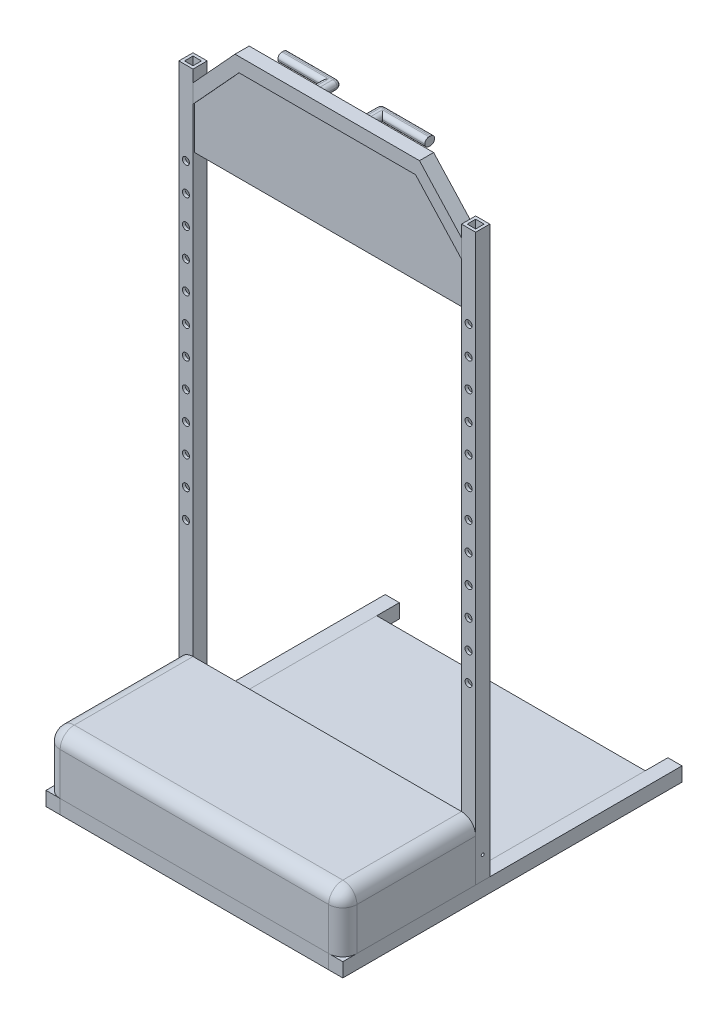
SolidWorks part; units mm, degrees
ref_plane "Front Plane" through (0, 0, 0) normal (0, 0, 1) x (1, 0, 0)
ref_plane "Top Plane" through (0, 0, 0) normal (0, 1, 0) x (1, 0, 0)
ref_plane "Right Plane" through (0, 0, 0) normal (1, 0, 0) x (0, 0, -1)
sketch "Sketch1" plane through (0, 0, 0) normal (0, 1, 0) x (1, 0, 0)
  line L0 (-525, -1151.5385) -> (-525, 48.4615)
  line L1 (-525, 48.4615) -> (-475, 48.4615)
  line L2 (-475, 48.4615) -> (-475, -1151.5385)
  line L3 (-475, -1151.5385) -> (-525, -1151.5385)
  line L4 (475, 48.4615) -> (475, -1151.5385)
  line L5 (475, -1151.5385) -> (525, -1151.5385)
  line L6 (525, -1151.5385) -> (525, 48.4615)
  line L7 (525, 48.4615) -> (475, 48.4615)
  line L8 (0, 0) -> (-475, 0)
  line L9 (0, 0) -> (475, 0)
  dimension "D1" = 50
  dimension "D2" = 50
  dimension "D3" = 475
  dimension "D4" = 475
  dimension "D5" = 1200
  dimension "D6" = 1200
extrude "Boss-Extrude1" add sketch "Sketch1" along normal blind 50 contours L3 L2 L1 L0 | L6 L7 L4 L5 region at (500, 0, 551.5385) region at (-500, 0, 551.5385)
sketch "Sketch2" plane through (0, 0, 0) normal (0, -1, 0) x (1, 0, 0)
  line L0 (-475, 1001.5385) -> (475, 1001.5385)
  line L1 (-475, -48.4615) -> (-475, 1151.5385) construction
  line L2 (475, -48.4615) -> (475, 1151.5385) construction
  line L3 (-475, 1001.5385) -> (-475, 1051.5385)
  line L4 (-475, 1051.5385) -> (475, 1051.5385)
  line L5 (475, 1051.5385) -> (475, 1001.5385)
  line L6 (-475, 1151.5385) -> (-475, 1001.5385)
  line M8 (475, 1151.5385) -> (475, -48.4615)
  dimension "D1" = 150
  dimension "D2" = 50
extrude "Boss-Extrude2" add sketch "Sketch2" against normal blind 50 separate body contours L4 L3 L0 M8 region at (0, 0, 1026.5385)
sketch "Sketch3" plane through (0, 50, 0) normal (0, 1, 0) x (1, 0, 0)
  line L11 (-525, -1151.5385) -> (-525, 48.4615) construction
  line L12 (-525, -681.5385) -> (-525, -631.5385)
  line L13 (-525, -631.5385) -> (-475, -631.5385)
  line L14 (-475, 48.4615) -> (-475, -1151.5385) construction
  line L15 (-475, -631.5385) -> (-475, -681.5385)
  line L16 (-475, -681.5385) -> (-525, -681.5385)
  line L17 (475, -681.5385) -> (475, -631.5385)
  line L19 (475, -631.5385) -> (525, -631.5385)
  line L21 (525, -631.5385) -> (525, -681.5385)
  line L22 (525, -681.5385) -> (475, -681.5385)
  point P0 (0, 0)
  dimension "D2" = 50
extrude "Boss-Extrude3" add sketch "Sketch3" along normal blind 2000 separate body
sketch "Sketch6" plane through (0, 0, 631.5385) normal (0, 0, -1) x (-1, 0, 0)
  line L1 (-475, 2050) -> (-475, 50) construction
  line L4 (475, 1942.6335) -> (430.5496, 1991.1256)
  line L7 (430.5496, 1991.1256) -> (312.4166, 2120)
  line L9 (-442.5309, 1978.0581) -> (-312.4312, 2120)
  line L10 (-326.3491, 2170) -> (326.3491, 2170)
  line L11 (-326.3491, 2170) -> (-475, 2007.8183)
  line L12 (326.3491, 2170) -> (475, 2007.8183)
  line L13 (475, 2050) -> (475, 50) construction
  line L15 (-475, 2007.8183) -> (-475, 1942.6335)
  line L16 (-312.4312, 2120) -> (312.4166, 2120)
  line L17 (475, 2007.8183) -> (475, 1942.6335)
  line L18 (-442.5309, 1978.0581) -> (-475, 1942.6335)
  dimension "D1" = 220
  dimension "D2" = 220
  dimension "D3" = 137.493
  dimension "D4" = 137.49
extrude "Boss-Extrude4" add sketch "Sketch6" against normal blind 50 separate body
sketch "Sketch8" plane through (0, 2050, 0) normal (0, 1, 0) x (1, 0, 0)
  line L0 (-515, -641.5385) -> (-515, -671.5385)
  line L1 (-515, -671.5385) -> (-485, -671.5385)
  line L2 (-485, -671.5385) -> (-485, -641.5385)
  line L3 (-485, -641.5385) -> (-515, -641.5385)
  line L4 (-525, -657.9132) -> (-515, -657.9132)
  line L5 (-525, -631.5385) -> (-525, -681.5385) construction
  line L6 (-491.9197, -671.5385) -> (-491.9197, -681.5385)
  line L8 (-500, -641.5385) -> (-500, -631.5385)
  line L9 (-475, -631.5385) -> (-525, -631.5385) construction
  line L10 (-485, -648.1401) -> (-475, -648.1401)
  line L11 (-475, -681.5385) -> (-475, -631.5385) construction
  line L12 (485, -671.5385) -> (485, -641.5385)
  line L13 (485, -641.5385) -> (515, -641.5385)
  line L14 (515, -641.5385) -> (515, -671.5385)
  line L15 (515, -671.5385) -> (485, -671.5385)
  line L16 (500, -671.5385) -> (500, -681.5385)
  line L17 (475, -681.5385) -> (525, -681.5385) construction
  line L18 (515, -657.9132) -> (525, -657.9132)
  line L19 (525, -681.5385) -> (525, -631.5385) construction
  line L20 (500, -641.5385) -> (500, -631.5385)
  line L22 (485, -657.9132) -> (475, -657.9132)
  line L23 (475, -631.5385) -> (475, -681.5385) construction
  point P10 (0, 0)
  point P40 (0, 0)
  dimension "D1" = 10
  dimension "D2" = 10
  dimension "D3" = 10
  dimension "D4" = 10
  dimension "D5" = 10
  dimension "D6" = 10
  dimension "D7" = 10
  dimension "D8" = 10
extrude "Cut-Extrude1" cut sketch "Sketch8" against normal blind 1980 contours L15 L14 L13 L12 | L2 L3 L0 L1 region at (-500, 2050, 656.5385) region at (500, 2050, 656.5385)
sketch "Sketch9" plane through (0, 50, 0) normal (0, 1, 0) x (1, 0, 0)
  line L0 (-525, -681.5385) -> (-525, -1151.5385)
  line L1 (-475, -1151.5385) -> (-525, -1151.5385) construction
  line L2 (-525, -1151.5385) -> (-525, 48.4615) construction
  line L3 (-525, -1151.5385) -> (525, -1151.5385)
  line L4 (525, -1151.5385) -> (525, -681.5385)
  line L5 (525, -681.5385) -> (-525, -681.5385)
  point P7 (0, 0)
  point P12 (0, 0)
  point P13 (0, 0)
  point P14 (0, 0)
extrude "Boss-Extrude5" add sketch "Sketch9" along normal blind 200 separate body
sketch "Sketch10" plane through (0, 0, 1001.5385) normal (0, 0, -1) x (-1, 0, 0)
  line L4 (-475, 50) -> (-475, 0)
  line L5 (-475, 0) -> (475, 0)
  line L7 (475, 0) -> (-475, 0) construction
  line L8 (475, 0) -> (475, 50)
  line L9 (475, 50) -> (-475, 50)
  point P2 (0, 0)
  point P3 (0, 0)
  point P4 (0, 0)
  point P6 (0, 0)
extrude "Boss-Extrude7" add sketch "Sketch10" along normal blind 320 separate body
sketch "Sketch11" plane through (0, 0, 1051.5385) normal (0, 0, 1) x (1, 0, 0)
  line L0 (-475, 50) -> (-475, 0)
  line L1 (-475, 0) -> (475, 0)
  line L2 (-475, 0) -> (475, 0) construction
  line L3 (475, 0) -> (475, 50)
  line L4 (475, 50) -> (-475, 50)
extrude "Boss-Extrude8" add sketch "Sketch11" along normal blind 100 separate body
fillet "Fillet1" radius 50 1 edges at (0, 250, 1151.5385)
fillet "Fillet2" radius 50 3 edges at (525, 125, 1151.5385) (525, 235.3553, 1136.8938) (525, 250, 891.5385)
fillet "Fillet3" radius 50 3 edges at (-525, 125, 1151.5385) (-525, 235.3553, 1136.8938) (-525, 250, 891.5385)
sketch "Sketch15" plane through (0, 0, 631.5385) normal (0, 0, -1) x (-1, 0, 0)
  line L0 (-525, 2050) -> (-525, 50) construction
  line L1 (-525, 1756.2545) -> (-475, 1756.2545)
  line L2 (-475, 2050) -> (-475, 50) construction
  line L3 (475, 1756.2545) -> (525, 1756.2545)
  line L4 (475, 2050) -> (475, 50) construction
  line L5 (525, 2050) -> (525, 50) construction
  circle A0 centre (-500, 1756.2545) radius 12.5
  circle A1 centre (500, 1756.2545) radius 12.5
  circle A2 centre (-500, 1656.2545) radius 12.5
  circle A3 centre (500, 1656.2545) radius 12.5
  circle A4 centre (-500, 1556.2545) radius 12.5
  circle A5 centre (500, 1556.2545) radius 12.5
  circle A6 centre (-500, 1456.2545) radius 12.5
  circle A7 centre (500, 1456.2545) radius 12.5
  circle A8 centre (-500, 1356.2545) radius 12.5
  circle A9 centre (500, 1356.2545) radius 12.5
  circle A10 centre (-500, 1256.2545) radius 12.5
  circle A11 centre (500, 1256.2545) radius 12.5
  circle A12 centre (-500, 1156.2545) radius 12.5
  circle A13 centre (500, 1156.2545) radius 12.5
  circle A14 centre (-500, 1056.2545) radius 12.5
  circle A15 centre (500, 1056.2545) radius 12.5
  circle A16 centre (-500, 956.2545) radius 12.5
  circle A17 centre (500, 956.2545) radius 12.5
  circle A18 centre (-500, 856.2545) radius 12.5
  circle A19 centre (500, 856.2545) radius 12.5
  circle A20 centre (-500, 756.2545) radius 12.5
  circle A21 centre (500, 756.2545) radius 12.5
  circle A22 centre (-500, 656.2545) radius 12.5
  circle A23 centre (500, 656.2545) radius 12.5
  dimension "D1" = 25
  dimension "D2" = 25
  dimension "D3" = 12
extrude "Cut-Extrude4" cut sketch "Sketch15" against normal blind 50 contours L1 A0 | L1 A0 | A2 | A4 | A6 | A8 | A10 | A12 | A14 | L3 A1 | L3 A1 | A3 | A5 | A7 | A9 | A16 | A18 | A20 | A22 | A11 | A13 | A15 | A17 | A19 | A21 | A23 region at (500, 1761.5597, 631.5385) region at (500, 1750.9494, 631.5385) region at (-500, 1761.5597, 631.5385) region at (-500, 1750.9494, 631.5385) region at (500, 1656.2545, 631.5385) region at (-500, 1656.2545, 631.5385) region at (500, 1556.2545, 631.5385) region at (-500, 1556.2545, 631.5385) region at (500, 1456.2545, 631.5385) region at (-500, 1456.2545, 631.5385) region at (500, 1356.2545, 631.5385) region at (-500, 1356.2545, 631.5385) region at (500, 1256.2545, 631.5385) region at (500, 1156.2545, 631.5385) region at (500, 1056.2545, 631.5385)
sketch "Sketch17" plane through (0, 0, 631.5385) normal (0, 0, -1) x (-1, 0, 0)
  line L0 (-475, 1942.6335) -> (-475, 1792.1994)
  line L1 (-475, 2050) -> (-475, 50) construction
  line L2 (-475, 1792.1994) -> (475, 1792.1994)
  line L3 (475, 2050) -> (475, 50) construction
  line L4 (475, 1792.1994) -> (475, 1942.6335)
  line L5 (475, 1942.6335) -> (312.4166, 2120)
  line L6 (312.4166, 2120) -> (475, 1942.6335) construction
  line L7 (312.4166, 2120) -> (-312.4312, 2120)
  line L8 (-312.4312, 2120) -> (-475, 1942.6335)
  dimension "D1" = 150.4341
extrude "Boss-Extrude13" add sketch "Sketch17" against normal blind 45 separate body
sketch "Sketch19" plane through (0, 0, 631.5385) normal (0, 0, -1) x (-1, 0, 0)
  line L0 (-272.3284, 1988.7665) -> (-272.3284, 1912.0744)
  line L1 (-272.3284, 1912.0744) -> (-242.3706, 1912.0744)
  line L2 (-242.3706, 1912.0744) -> (-242.3706, 1960.9057)
  line L3 (-242.3706, 1960.9057) -> (-180.3579, 1960.9057)
  line L4 (-180.3579, 1960.9057) -> (-180.3579, 1988.7665)
  line L5 (-180.3579, 1988.7665) -> (-272.3284, 1988.7665)
  line L6 (-141.1131, 1988.7665) -> (-141.1131, 1912.0744)
  line L7 (-141.1131, 1912.0744) -> (-112.9528, 1912.0744)
  line L8 (-112.9528, 1912.0744) -> (-112.9528, 1988.7665)
  line L9 (-112.9528, 1988.7665) -> (-141.1131, 1988.7665)
  line L10 (-48.2439, 2017.8255) -> (-48.2439, 1912.0744)
  line L11 (-48.2439, 1912.0744) -> (-18.8852, 1912.0744)
  line L12 (-18.8852, 1912.0744) -> (-18.8852, 2017.8255)
  line L13 (-18.8852, 2017.8255) -> (17.0642, 2017.8255)
  line L14 (17.0642, 2017.8255) -> (17.0642, 2045.9859)
  line L15 (17.0642, 2045.9859) -> (-90.784, 2045.9859)
  line L16 (-90.784, 2045.9859) -> (-90.784, 2017.8255)
  line L17 (-90.784, 2017.8255) -> (-48.2439, 2017.8255)
  line L18 (71.8777, 2017.8255) -> (71.8777, 1912.0744)
  line L19 (71.8777, 1912.0744) -> (99.773, 1912.0744)
  line L20 (99.773, 1912.0744) -> (99.773, 2017.8255)
  line L21 (99.773, 2017.8255) -> (142.35, 2017.8255)
  line L22 (142.35, 2017.8255) -> (142.35, 2045.9859)
  line L23 (142.35, 2045.9859) -> (33.4606, 2045.9859)
  line L24 (33.4606, 2045.9859) -> (33.4606, 2017.8255)
  line L25 (33.4606, 2017.8255) -> (71.8777, 2017.8255)
  line L26 (160.7022, 1988.7665) -> (160.7022, 1912.0744)
  line L27 (160.7022, 1912.0744) -> (187.3739, 1912.0744)
  line L28 (187.3739, 1912.0744) -> (187.3739, 1958.7508)
  line L29 (198.1476, 1960.9057) -> (242.0166, 1912.0744)
  line L30 (242.0166, 1912.0744) -> (275.9419, 1912.0744)
  line L31 (275.9419, 1912.0744) -> (232.0729, 1960.9057)
  line L32 (160.7022, 1988.7665) -> (232.0729, 1988.7665)
  line L33 (160.7022, 2045.9859) -> (160.7022, 2017.8255)
  line L34 (160.7022, 2017.8255) -> (232.0729, 2017.8255)
  line L35 (160.7022, 2045.9859) -> (232.0729, 2045.9859)
  line L36 (-272.3284, 2003.4296) -> (-246.6703, 2003.4296)
  line L37 (-226.9126, 2017.8255) -> (-163.753, 2017.8255)
  line L38 (-163.753, 2017.8255) -> (-163.753, 2045.9859)
  line L39 (-163.753, 2045.9859) -> (-226.9126, 2045.9859)
  line L40 (-226.9126, 2045.9859) -> (-238.7348, 2045.9859)
  line L41 (-136.9779, 1873.4631) -> (-136.9779, 1826.4801)
  line L42 (-136.9779, 1826.4801) -> (-109.9029, 1826.4801)
  line L43 (-136.9779, 1873.4631) -> (-109.9029, 1873.4631)
  line L44 (-125.1753, 1862.599) -> (-125.1753, 1856.5312)
  line L45 (-125.1753, 1856.5312) -> (-112.9528, 1856.5312)
  line L46 (-125.1753, 1862.599) -> (-112.9528, 1862.599)
  line L47 (-125.1753, 1845.9513) -> (-125.1753, 1839.5724)
  line L48 (-125.1753, 1839.5724) -> (-112.9528, 1839.5724)
  line L49 (-125.1753, 1845.9513) -> (-112.9528, 1845.9513)
  line L50 (-112.9528, 1845.9513) -> (-109.9029, 1845.9513)
  line L51 (-112.9528, 1839.5724) -> (-109.9029, 1839.5724)
  line L52 (-85.0343, 1873.4631) -> (-66.6752, 1842.7619)
  line L53 (-66.6752, 1842.7619) -> (-66.6752, 1826.4801)
  line L54 (-66.6752, 1826.4801) -> (-57.4956, 1826.4801)
  line L55 (-57.4956, 1826.4801) -> (-57.4956, 1842.7619)
  line L56 (-57.4956, 1842.7619) -> (-41.4704, 1873.4631)
  line L57 (-41.4704, 1873.4631) -> (-50.1843, 1873.4631)
  line L58 (-50.1843, 1873.4631) -> (-62.0854, 1858.1125)
  line L59 (-62.0854, 1858.1125) -> (-75.8547, 1873.4631)
  line L60 (-75.8547, 1873.4631) -> (-85.0343, 1873.4631)
  line L61 (4.7086, 1873.4631) -> (4.7086, 1826.4801)
  line L62 (4.7086, 1826.4801) -> (13.2284, 1826.4801)
  line L63 (13.2284, 1826.4801) -> (13.2284, 1839.5724)
  line L64 (4.7086, 1873.4631) -> (28.4157, 1873.4631)
  line L65 (15.2657, 1862.599) -> (15.2657, 1851.9624)
  line L66 (15.2657, 1851.9624) -> (26.008, 1851.9624)
  line L67 (15.2657, 1862.599) -> (26.008, 1862.599)
  line L68 (22.0959, 1839.5724) -> (33.4606, 1826.4801)
  line L69 (33.4606, 1826.4801) -> (45.4406, 1826.4801)
  line L70 (45.4406, 1826.4801) -> (32.4677, 1841.4251)
  line L71 (62.3238, 1873.4631) -> (62.3238, 1826.4801)
  line L72 (62.3238, 1826.4801) -> (71.8777, 1826.4801)
  line L73 (71.8777, 1826.4801) -> (71.8777, 1873.4631)
  line L74 (71.8777, 1873.4631) -> (62.3238, 1873.4631)
  circle A0 centre (-127.033, 2031.1227) radius 13.873
  circle A1 centre (-199.4893, 1851.9624) radius 11.2617
  circle A2 centre (198.1476, 1851.9624) radius 12.096
  arc A3 (232.0729, 2017.8255) -> (232.0729, 1988.7665) centre (228.8278, 2003.296) cw
  arc A4 (232.0729, 2045.9859) -> (232.0729, 1960.9057) centre (230.1472, 2003.4458) cw
  arc A5 (-272.3284, 2003.4296) -> (-238.7348, 2045.9859) centre (-233.4063, 2007.2423) cw
  arc A6 (-246.6703, 2003.4296) -> (-226.9126, 2017.8255) centre (-227.5737, 1997.9766) cw
  arc A7 (-109.9029, 1873.4631) -> (-102.1486, 1851.9624) centre (-113.2015, 1860.1248) cw
  arc A8 (-109.9029, 1826.4801) -> (-102.1486, 1851.9624) centre (-113.2682, 1841.4251) ccw
  arc A9 (-112.9528, 1862.599) -> (-112.9528, 1856.5312) centre (-112.8849, 1859.5651) cw
  arc A10 (-109.9029, 1845.9513) -> (-109.9029, 1839.5724) centre (-111.2845, 1842.7619) cw
  arc A11 (26.008, 1862.599) -> (26.008, 1851.9624) centre (26.0805, 1857.2807) cw
  arc A12 (28.4157, 1873.4631) -> (32.4677, 1841.4251) centre (26.7494, 1856.9771) cw
  arc A13 (13.2284, 1839.5724) -> (22.0959, 1839.5724) centre (17.6621, 1834.6146) cw
  circle A14 centre (115.4352, 1851.9624) radius 12.8515
  circle A15 centre (115.4352, 1851.9624) radius 25.4976
  arc A16 (187.3739, 1958.7508) -> (198.1476, 1960.9057) centre (193.2488, 1957.3882) cw
extrude "Boss-Extrude14" add sketch "Sketch19" along normal blind 10 separate body
sketch "Sketch21" plane through (0, 0, 631.5385) normal (0, 0, -1) x (-1, 0, 0)
  line L0 (-270, 1792.1994) -> (0, 1792.1994)
  line L1 (-475, 1792.1994) -> (475, 1792.1994) construction
  line L2 (0, 1792.1994) -> (270, 1792.1994)
  line L3 (270, 1792.1994) -> (145.7896, 1644.1712)
  line L4 (145.7896, 1644.1712) -> (-145.7896, 1644.1712)
  line L5 (-145.7896, 1644.1712) -> (-270, 1792.1994)
  line L6 (-132.9099, 1690.9003) -> (132.3288, 1690.9003)
  line L9 (-217.9099, 1792.1994) -> (-132.9099, 1690.9003)
  line L10 (217.3288, 1792.1994) -> (132.3288, 1690.9003)
  line M9 (-475, 1792.1994) -> (475, 1792.1994)
  dimension "D1" = 130
  dimension "D2" = 130
  dimension "D3" = 270
  dimension "D4" = 270
  dimension "D5" = 130
  dimension "D6" = 130
  dimension "D7" = 85
  dimension "D8" = 85
extrude "Boss-Extrude16" [suppressed] add sketch "Sketch21" against normal blind 40 separate body contours L2 L10 L6 L9 L5 L4 L3 M9
sketch "Sketch25" plane through (0, 0, 631.5385) normal (0, 0, -1) x (-1, 0, 0)
  line L0 (-326.3491, 2170) -> (326.3491, 2170)
  line L1 (0, 2170) -> (-0.0073, 2120)
  line L2 (-312.4312, 2120) -> (312.4166, 2120) construction
  line L3 (-0.0037, 2145) -> (-90.0037, 2145)
  line L4 (-0.0037, 2145) -> (89.9963, 2145)
  line L6 (-110.0037, 2160) -> (-70.0037, 2160)
  line L7 (-110.0037, 2160) -> (-110.0037, 2130)
  line L8 (-110.0037, 2130) -> (-70.0037, 2130)
  line L9 (-70.0037, 2160) -> (-70.0037, 2130)
  line L10 (-110.0037, 2160) -> (-70.0037, 2130) construction
  line L11 (-110.0037, 2130) -> (-70.0037, 2160) construction
  line L12 (69.9963, 2160) -> (109.9963, 2160)
  line L13 (69.9963, 2160) -> (69.9963, 2130)
  line L14 (69.9963, 2130) -> (109.9963, 2130)
  line L15 (109.9963, 2160) -> (109.9963, 2130)
  line L16 (69.9963, 2160) -> (109.9963, 2130) construction
  line L17 (69.9963, 2130) -> (109.9963, 2160) construction
  dimension "D1" = 40
  dimension "D2" = 40
  dimension "D3" = 30
  dimension "D4" = 30
  dimension "D5" = 90
  dimension "D6" = 90
extrude "Boss-Extrude23" add sketch "Sketch25" along normal blind 70 contours L9 L6 L7 L8 | L15 L12 L13 L14 region at (70.5037, 2137.5, 631.5385) region at (-70.4963, 2152.5, 631.5385)
sketch "Sketch28" plane through (110.0037, 0, 0) normal (1, 0, 0) x (0, 0, -1)
  line L0 (-561.5385, 2160) -> (-631.5385, 2160) construction
  line L1 (-596.5385, 2160) -> (-561.5385, 2160)
  line L2 (-596.5385, 2160) -> (-596.5385, 2130)
  line L3 (-596.5385, 2130) -> (-561.5385, 2130)
  line L4 (-561.5385, 2160) -> (-561.5385, 2130)
  dimension "D1" = 35
extrude "Boss-Extrude24" add sketch "Sketch28" along normal blind 150
sketch "Sketch29" plane through (-109.9963, 0, 0) normal (-1, 0, 0) x (0, 0, 1)
  line L0 (561.5385, 2130) -> (631.5385, 2130) construction
  line L1 (561.5385, 2160) -> (596.5385, 2160)
  line L2 (561.5385, 2160) -> (561.5385, 2130)
  line L3 (561.5385, 2130) -> (596.5385, 2130)
  line L4 (596.5385, 2160) -> (596.5385, 2130)
  dimension "D1" = 35
extrude "Boss-Extrude25" add sketch "Sketch29" along normal blind 150
fillet "Fillet4" radius 15 16 edges at (-109.9963, 2130, 614.0385) (-69.9963, 2130, 596.5385) (110.0037, 2130, 614.0385) (-69.9963, 2160, 596.5385) (-109.9963, 2160, 614.0385) (110.0037, 2160, 614.0385) (70.0037, 2130, 596.5385) (70.0037, 2160, 596.5385) (-184.9963, 2160, 596.5385) (-184.9963, 2130, 596.5385) (-164.9963, 2130, 561.5385) (-164.9963, 2160, 561.5385) (185.0037, 2130, 596.5385) (185.0037, 2160, 596.5385) (165.0037, 2130, 561.5385) (165.0037, 2160, 561.5385)
fillet "Fillet5" radius 15 2 edges at (74.3971, 2134.3934, 565.9319) (74.3971, 2155.6066, 565.9319)
fillet "Fillet6" radius 15 2 edges at (-74.3897, 2134.3934, 565.9319) (-74.3897, 2155.6066, 565.9319)
sketch "Sketch30" plane through (0, 0, 631.5385) normal (0, 0, -1) x (-1, 0, 0)
  line L17 (-512.5, 185) -> (-487.5, 185)
  line L18 (-512.5, 185) -> (-512.5, 75)
  line L19 (-512.5, 75) -> (-487.5, 75)
  line L20 (-487.5, 185) -> (-487.5, 75)
  line L21 (487.5, 185) -> (512.5, 185)
  line L22 (487.5, 185) -> (487.5, 75)
  line L23 (487.5, 75) -> (512.5, 75)
  line L24 (512.5, 185) -> (512.5, 75)
  line L25 (-525, 2050) -> (-525, 50) construction
  line L27 (525, 2050) -> (525, 50) construction
  dimension "D2" = 25
  dimension "D3" = 12.5
  dimension "D4" = 110
  dimension "D6" = 110
  dimension "D7" = 25
  dimension "D8" = 12.5
extrude "Cut-Extrude5" cut sketch "Sketch30" against normal blind 100
sketch "Sketch31" plane through (525, 0, 0) normal (1, 0, 0) x (0, 0, -1)
  line L0 (-681.5385, 50) -> (-631.5385, 50)
  line L1 (-656.5385, 50) -> (-656.5385, 130)
  circle A0 centre (-656.5385, 130) radius 5.25
  point P7 (0, 0)
  point P8 (0, 0)
  dimension "D2" = 10.5
  dimension "D1" = 80
extrude "Cut-Extrude6" cut sketch "Sketch31" against normal blind 55 contours A0 region at (525, 126.3927, 652.9312)
sketch "Sketch32" plane through (-525, 0, 0) normal (-1, 0, 0) x (0, 0, 1)
  line L0 (631.5385, 50) -> (681.5385, 50)
  line L1 (656.5385, 50) -> (656.5385, 130)
  circle A0 centre (656.5385, 130) radius 5.25
  point P7 (0, 0)
  point P8 (0, 0)
  dimension "D2" = 10.5
  dimension "D1" = 80
extrude "Cut-Extrude7" cut sketch "Sketch32" against normal blind 55 contours A0 region at (-525, 126.3927, 660.1458)
sketch "Sketch33" [suppressed] plane through (0, 0, 631.5385) normal (0, 0, -1) x (-1, 0, 0)
  line L0 (-131.6259, 1690.9003) -> (-131.6259, 1644.1712)
  line L1 (-132.9099, 1690.9003) -> (132.3288, 1690.9003) construction
  line L2 (145.7896, 1644.1712) -> (-145.7896, 1644.1712) construction
  line L3 (-131.6259, 1644.1712) -> (132.3288, 1644.1712)
  line L4 (132.3288, 1644.1712) -> (132.3288, 1690.9003)
  line L5 (132.3288, 1690.9003) -> (-131.6259, 1690.9003)
  line L7 (-32.4678, 1744.2476) -> (27.5322, 1744.2476)
  line L8 (-32.4678, 1744.2476) -> (-32.4678, 1594.2476)
  line L9 (-32.4678, 1594.2476) -> (27.5322, 1594.2476)
  line L10 (27.5322, 1744.2476) -> (27.5322, 1594.2476)
  line L11 (-32.4678, 1744.2476) -> (27.5322, 1594.2476) construction
  line L12 (-32.4678, 1594.2476) -> (27.5322, 1744.2476) construction
  point P11 (-2.4678, 1669.2476)
  dimension "D1" = 60
  dimension "D2" = 150
extrude "Boss-Extrude26" [suppressed] add sketch "Sketch33" along normal blind 10 contours L10 L3 L8 L9 | L10 L5 L8 L3 | L10 L7 L8 L5
sketch "Sketch34" [suppressed] plane through (32.4678, 0, 0) normal (1, 0, 0) x (0, 0, -1)
  line L0 (-621.5385, 1744.2476) -> (-610.9229, 1738.1187)
  line L1 (-610.9229, 1738.1187) -> (-610.9229, 1708.1187)
  line L2 (-610.9229, 1708.1187) -> (-619.1155, 1703.3887)
  line L3 (-621.5385, 1744.2476) -> (-621.5385, 1594.2476)
  line L4 (-619.1155, 1703.3887) -> (-619.1155, 1673.3887)
  line L5 (-619.1155, 1673.3887) -> (-610.9229, 1668.6587)
  line L6 (-619.1155, 1633.9287) -> (-619.1155, 1602.9729)
  line L7 (-610.9229, 1668.6587) -> (-610.9229, 1638.6587)
  line L9 (-610.9229, 1638.6587) -> (-619.1155, 1633.9287)
  line L10 (-619.1155, 1602.9729) -> (-610.9229, 1594.2476)
  line L11 (-610.9229, 1594.2476) -> (-621.5385, 1594.2476)
  dimension "D1" = 120
  dimension "D2" = 120
  dimension "D3" = 30
  dimension "D4" = 120
  dimension "D5" = 30
  dimension "D6" = 30
  dimension "D7" = 120
  dimension "D8" = 136.803
extrude "Boss-Extrude27" [suppressed] add sketch "Sketch34" against normal blind 5
sketch "Sketch35" [suppressed] plane through (-27.5322, 0, 0) normal (-1, 0, 0) x (0, 0, 1)
  line L0 (621.5385, 1744.2476) -> (621.5385, 1594.2476)
  line L1 (621.5385, 1594.2476) -> (610.9229, 1594.2476)
  line L2 (610.9229, 1594.2476) -> (619.1155, 1602.9729)
  line L3 (619.1155, 1602.9729) -> (619.1155, 1633.9287)
  line L4 (619.1155, 1633.9287) -> (610.9229, 1638.6587)
  line L5 (610.9229, 1638.6587) -> (610.9229, 1668.6587)
  line L6 (610.9229, 1668.6587) -> (619.1155, 1673.3887)
  line L7 (619.1155, 1673.3887) -> (619.1155, 1703.3887)
  line L8 (619.1155, 1703.3887) -> (610.9229, 1708.1187)
  line L9 (610.9229, 1708.1187) -> (610.9229, 1738.1187)
  line L10 (610.9229, 1738.1187) -> (621.5385, 1744.2476)
extrude "Boss-Extrude28" [suppressed] add sketch "Sketch35" against normal blind 5
sketch "Sketch36" [suppressed] plane through (0, 1594.2476, 0) normal (0, -1, 0) x (1, 0, 0)
  line L0 (-22.5322, 611.091) -> (-5.5322, 611.091)
  line L1 (-22.5322, 610.9229) -> (-22.5322, 621.5385) construction
  line L2 (-5.5322, 611.091) -> (-1.5322, 618.0192)
  line L3 (-1.5322, 618.0192) -> (6.4678, 618.0192)
  line L4 (6.4678, 618.0192) -> (10.4678, 611.091)
  line L5 (10.4678, 611.091) -> (27.4678, 611.091)
  line L6 (27.4678, 621.5385) -> (27.4678, 610.9229) construction
  line L7 (27.4678, 611.091) -> (27.4678, 621.5385)
  line L8 (27.4678, 621.5385) -> (-22.5322, 621.5385)
  line L9 (-22.5322, 621.5385) -> (-22.5322, 611.091)
  dimension "D1" = 120
  dimension "D2" = 120
  dimension "D3" = 4
  dimension "D4" = 4
  dimension "D5" = 17
  dimension "D6" = 17
extrude "Boss-Extrude29" [suppressed] add sketch "Sketch36" against normal blind 5
sketch "Sketch37" [suppressed] plane through (0, 0, 611.091) normal (0, 0, -1) x (-1, 0, 0)
  line L0 (-10.4678, 1599.2476) -> (-27.4678, 1599.2476)
  line L1 (-27.4678, 1599.2476) -> (-27.4678, 1606.139)
  line L2 (-27.4678, 1606.139) -> (-10.4678, 1606.139)
  line L3 (-10.4678, 1606.139) -> (-10.4678, 1599.2476)
  line L4 (5.5322, 1599.2476) -> (5.5322, 1606.139)
  line L7 (22.5322, 1599.2476) -> (5.5322, 1599.2476)
  line L8 (22.5322, 1599.2476) -> (22.5322, 1606.139)
  line L9 (22.5322, 1606.139) -> (5.5322, 1606.139)
extrude "Boss-Extrude30" [suppressed] add sketch "Sketch37" against normal blind 2
fillet "Fillet8" [suppressed] radius 1
fillet "Fillet9" [suppressed] radius 5
sketch "Sketch38" plane through (0, 0, 0) normal (0, -1, 0) x (1, 0, 0)
  line L1 (-475, 681.5385) -> (475, 681.5385)
  line L2 (-475, 681.5385) -> (-475, 31.5385)
  line L3 (-475, 31.5385) -> (475, 31.5385)
  line L4 (475, 681.5385) -> (475, 31.5385)
  point P7 (0, 0)
  dimension "D2" = 650
  dimension "D3" = 950
extrude "Boss-Extrude31" add sketch "Sketch38" against normal blind 35 separate body
sketch "Sketch39" plane through (0, 35, 0) normal (0, 1, 0) x (1, 0, 0)
  line L5 (-475, -31.5385) -> (475, -31.5385)
  line L6 (-475, -31.5385) -> (-475, -681.5385)
  line L7 (-475, -681.5385) -> (475, -681.5385)
  line L8 (475, -31.5385) -> (475, -681.5385)
extrude "Boss-Extrude33" add sketch "Sketch39" along normal blind 15 separate body
